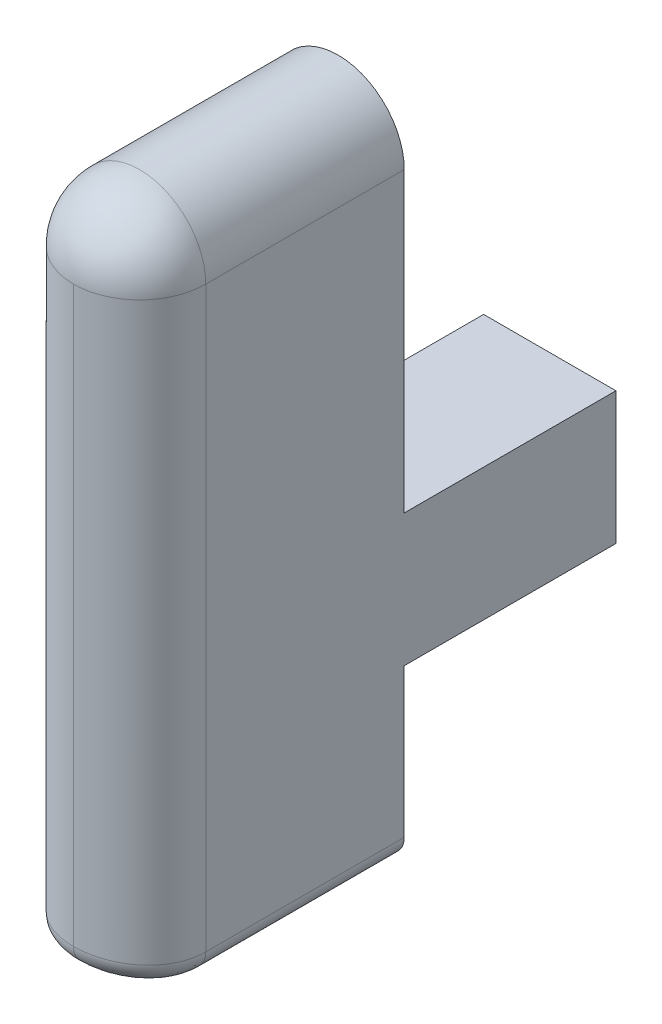
SolidWorks part; units mm, degrees
ref_plane "Front Plane" through (0, 0, 0) normal (0, 0, 1) x (1, 0, 0)
ref_plane "Top Plane" through (0, 0, 0) normal (0, 1, 0) x (1, 0, 0)
ref_plane "Right Plane" through (0, 0, 0) normal (1, 0, 0) x (0, 0, -1)
sketch "Sketch1" plane through (0, 0, 0) normal (0, 0, 1) x (1, 0, 0)
  line L0 (30.48, -147.1681) -> (30.48, -155.893) construction
  line L3 (31.369, -150.6415) -> (29.591, -152.4195) construction
  line L5 (29.6863, -147.1681) -> (29.6863, -155.893)
  line L6 (31.2738, -147.1681) -> (31.2738, -155.893)
  arc A0 (29.6863, -147.1681) -> (31.2738, -147.1681) centre (30.48, -147.1681) cw
  arc A1 (29.6863, -155.893) -> (31.2738, -155.893) centre (30.48, -155.893) ccw
  point P3 (30.48, -151.5305)
  dimension "D1" = 0.7937
  dimension "D2" = 0.7937
extrude "Boss-Extrude1" add sketch "Sketch1" along normal blind 3.175
sketch "Sketch3" plane through (0, 0, 0) normal (0, 0, -1) x (-1, 0, 0)
  line L0 (-30.48, -146.3743) -> (-30.48, -156.6867) construction
  line L2 (-29.6863, -152.3243) -> (-31.2738, -152.3243)
  line L3 (-29.6863, -152.3243) -> (-29.6863, -150.7368)
  line L4 (-29.6863, -150.7368) -> (-31.2738, -150.7368)
  line L5 (-31.2738, -152.3243) -> (-31.2738, -150.7368)
  line L6 (-29.6863, -152.3243) -> (-31.2738, -150.7368) construction
  line L7 (-29.6863, -150.7368) -> (-31.2738, -152.3243) construction
  arc A0 (-29.6863, -147.1681) -> (-31.2738, -147.1681) centre (-30.48, -147.1681) ccw construction
  arc A1 (-31.2738, -155.893) -> (-29.6863, -155.893) centre (-30.48, -155.893) ccw construction
  point P8 (-30.48, -151.5305)
  dimension "D1" = 1.5875
extrude "Boss-Extrude2" add sketch "Sketch3" along normal blind 2.54
fillet "Fillet1" radius 0.7937 4 edges at (31.2738, -151.5305, 3.175) (30.48, -156.6867, 3.175) (29.6863, -151.5305, 3.175) (30.48, -146.3743, 3.175)
sketch "Sketch4" plane through (0, 0, 0) normal (0, 0, 1) x (1, 0, 0)
  circle A1 centre (30.48, -146.5331) radius 2.3812
extrude "Cut-Extrude1" [suppressed] cut sketch "Sketch4" along normal through all
fillet "Fillet2" [suppressed] radius 0.254 tangent propagation no
sketch "Sketch6" plane through (0, 0, 0) normal (0, 0, 1) x (1, 0, 0)
  circle A0 centre (30.48, -156.6867) radius 2.3812
  circle A1 centre (30.48, -146.5331) radius 2.3812 construction
  arc A2 (29.6863, -155.893) -> (31.2738, -155.893) centre (30.48, -155.893) ccw construction
extrude "Cut-Extrude2" cut sketch "Sketch6" along normal through all
fillet "Fillet3" radius 0.254 4 edges at (31.2738, -154.4417, 1.1906) (30.9607, -154.3545, 3.0129) (29.8477, -154.391, 2.8611) (29.6863, -154.4417, 1.1906)
